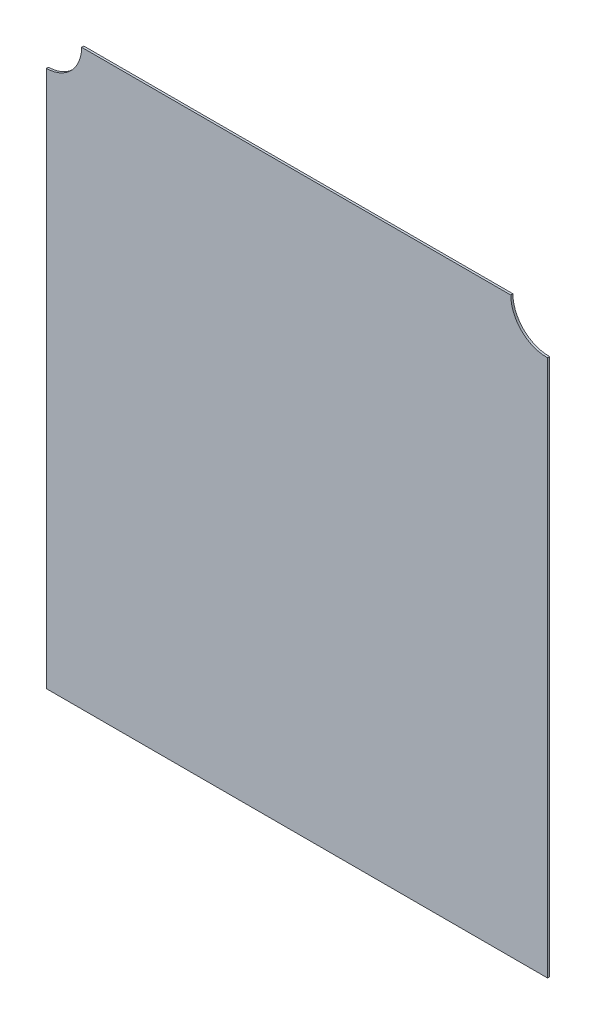
SolidWorks part; units mm, degrees
material "ДСП"
ref_plane "Спереди" through (0, 0, 0) normal (0, 0, 1) x (1, 0, 0)
ref_plane "Сверху" through (0, 0, 0) normal (0, 1, 0) x (1, 0, 0)
ref_plane "Справа" through (0, 0, 0) normal (1, 0, 0) x (0, 0, -1)
sketch "Эскиз1" plane through (0, 0, 0) normal (0, 0, 1) x (1, 0, 0)
  line L1 (0, 0) -> (696, 0)
  line L2 (0, 0) -> (0, 796)
  line L3 (0, 796) -> (696, 796)
  line L4 (696, 0) -> (696, 796)
  dimension "D1" = 796
  dimension "D2" = 696
extrude "Придание толщины" add sketch "Эскиз1" along normal blind 3
sketch "Эскиз3" plane through (0, 0, 3) normal (0, 0, 1) x (1, 0, 0)
  line L0 (0, 796) -> (0, 0) construction
  line L1 (0, 0) -> (696, 0) construction
  circle A0 centre (-1, 796) radius 50
  dimension "D1" = 100
  dimension "D2" = 1
  dimension "D3" = 796
extrude "Отверстие 1" cut sketch "Эскиз3" against normal blind 3
sketch "Эскиз4" plane through (0, 0, 3) normal (0, 0, 1) x (1, 0, 0)
  line L0 (0, 746.01) -> (0, 0) construction
  line L1 (0, 0) -> (696, 0) construction
  circle A0 centre (695, 796) radius 50
  dimension "D3" = 100
  dimension "D1" = 695
  dimension "D2" = 796
extrude "Отверстие 2" cut sketch "Эскиз4" against normal blind 3
sketch "Эскиз5" plane through (0, 0, 3) normal (0, 0, 1) x (1, 0, 0)
  line L0 (0, 746.01) -> (0, 0) construction
  line L1 (0, 0) -> (696, 0) construction
  circle A0 centre (0, 0) radius 4
  dimension "D1" = 8
extrude "Отверстие 3" [suppressed] cut sketch "Эскиз5" against normal blind 16
sketch "Эскиз6" plane through (0, 0, 3) normal (0, 0, 1) x (1, 0, 0)
  line L0 (0, 746.01) -> (0, 0) construction
  line L1 (0, 0) -> (696, 0) construction
  circle A0 centre (0, 0) radius 4
  dimension "D1" = 8
extrude "Отверстие 4" [suppressed] cut sketch "Эскиз6" against normal blind 16
sketch "Эскиз7" plane through (0, 0, 3) normal (0, 0, 1) x (1, 0, 0)
  line L0 (0, 746.01) -> (0, 0) construction
  line L1 (0, 0) -> (696, 0) construction
  circle A0 centre (0, 0) radius 4
  dimension "D1" = 8
extrude "Отверстие 5" [suppressed] cut sketch "Эскиз7" against normal blind 16
sketch "Эскиз8" plane through (0, 0, 3) normal (0, 0, 1) x (1, 0, 0)
  line L0 (0, 746.01) -> (0, 0) construction
  line L1 (0, 0) -> (696, 0) construction
  circle A0 centre (0, 0) radius 4
  dimension "D1" = 8
extrude "Отверстие 6" [suppressed] cut sketch "Эскиз8" against normal blind 16
sketch "Эскиз9" plane through (0, 0, 3) normal (0, 0, 1) x (1, 0, 0)
  line L0 (0, 746.01) -> (0, 0) construction
  line L1 (0, 0) -> (696, 0) construction
  circle A0 centre (0, 0) radius 4
  dimension "D1" = 8
extrude "Отверстие 7" [suppressed] cut sketch "Эскиз9" against normal blind 16
sketch "Эскиз10" plane through (0, 0, 3) normal (0, 0, 1) x (1, 0, 0)
  line L0 (0, 746.01) -> (0, 0) construction
  line L1 (0, 0) -> (696, 0) construction
  circle A0 centre (0, 0) radius 4
  dimension "D1" = 8
extrude "Отверстие 8" [suppressed] cut sketch "Эскиз10" against normal blind 16
sketch "Эскиз27" plane through (0, 0, 3) normal (0, 0, 1) x (1, 0, 0)
  line L2 (0, 746.01) -> (0, 0) construction
  line L3 (0, 0) -> (696, 0) construction
  circle A0 centre (0, 0) radius 4
  dimension "D1" = 8
  dimension "D3" = 0
extrude "Отверстие 9" [suppressed] cut sketch "Эскиз27" against normal blind 10
sketch "Эскиз29" plane through (0, 0, 3) normal (0, 0, 1) x (1, 0, 0)
  line L2 (0, 746.01) -> (0, 0) construction
  line L3 (0, 0) -> (696, 0) construction
  circle A0 centre (0, 0) radius 4
  dimension "D1" = 8
extrude "Отверстие 10" [suppressed] cut sketch "Эскиз29" against normal blind 10
sketch "Эскиз30" plane through (0, 0, 3) normal (0, 0, 1) x (1, 0, 0)
  line L1 (0, 0) -> (696, 0) construction
  line L3 (0, 746.01) -> (0, 0) construction
  circle A0 centre (0, 0) radius 4
  dimension "D1" = 8
extrude "Отверстие 11" [suppressed] cut sketch "Эскиз30" against normal blind 10
sketch "Эскиз31" plane through (0, 0, 3) normal (0, 0, 1) x (1, 0, 0)
  line L2 (0, 0) -> (696, 0) construction
  line L3 (0, 746.01) -> (0, 0) construction
  circle A0 centre (0, 0) radius 4
  dimension "D1" = 8
extrude "Отверстие 12" [suppressed] cut sketch "Эскиз31" against normal blind 10
sketch "Эскиз11" plane through (0, 796, 0) normal (0, 1, 0) x (1, 0, 0)
  line L0 (0, -3) -> (0, 0) construction
  line L1 (645, -3) -> (49, -3) construction
  circle A0 centre (0, -3) radius 2.5
  dimension "D3" = 0
  dimension "D1" = 5
extrude "Отверстие А1" [suppressed] cut sketch "Эскиз11" against normal blind 37
sketch "Эскиз12" plane through (0, 796, 0) normal (0, 1, 0) x (1, 0, 0)
  line L1 (0, -3) -> (0, 0) construction
  line L2 (645, -3) -> (49, -3) construction
  circle A0 centre (0, 5) radius 2.5
  dimension "D1" = 5
  dimension "D3" = 8
extrude "Отверстие А2" [suppressed] cut sketch "Эскиз12" against normal blind 37
sketch "Эскиз13" plane through (0, 796, 0) normal (0, 1, 0) x (1, 0, 0)
  line L1 (0, -3) -> (0, 0) construction
  line L2 (645, -3) -> (49, -3) construction
  circle A0 centre (0, -3) radius 4
  dimension "D1" = 8
  dimension "D3" = 0
extrude "Отверстие А3" [suppressed] cut sketch "Эскиз13" against normal blind 20
sketch "Эскиз14" plane through (0, 796, 0) normal (0, 1, 0) x (1, 0, 0)
  line L0 (0, -3) -> (0, 0) construction
  line L1 (645, -3) -> (49, -3) construction
  circle A0 centre (0, 5) radius 4
  dimension "D1" = 8
  dimension "D3" = 8
extrude "Отверстие А4" [suppressed] cut sketch "Эскиз14" against normal blind 20
sketch "Эскиз15" plane through (696, 0, 0) normal (1, 0, 0) x (0, 0, -1)
  line L0 (-3, 796) -> (0, 796) construction
  line L1 (-3, 0) -> (-3, 746.01) construction
  circle A0 centre (-3, 796) radius 2.5
  dimension "D2" = 0
  dimension "D3" = 0
  dimension "D1" = 5
extrude "Отверстие В1" [suppressed] cut sketch "Эскиз15" against normal blind 37
sketch "Эскиз16" plane through (696, 0, 0) normal (1, 0, 0) x (0, 0, -1)
  line L0 (-3, 796) -> (0, 796) construction
  line L1 (-3, 0) -> (-3, 746.01) construction
  circle A0 centre (-3, 796) radius 2.5
  dimension "D1" = 5
extrude "Отверстие В2" [suppressed] cut sketch "Эскиз16" against normal blind 37
sketch "Эскиз17" plane through (696, 0, 0) normal (1, 0, 0) x (0, 0, -1)
  line L1 (-3, 796) -> (0, 796) construction
  line L2 (-3, 0) -> (-3, 746.01) construction
  circle A0 centre (-3, 796) radius 4
  dimension "D1" = 8
  dimension "D2" = 0
  dimension "D3" = 0
extrude "Отверстие В3" [suppressed] cut sketch "Эскиз17" against normal blind 20
sketch "Эскиз18" plane through (696, 0, 0) normal (1, 0, 0) x (0, 0, -1)
  line L0 (-3, 796) -> (0, 796) construction
  line L1 (-3, 0) -> (-3, 746.01) construction
  circle A0 centre (-3, 796) radius 4
  dimension "D3" = 0
  dimension "D2" = 8
  dimension "D1" = 0
extrude "Отверстие В4" [suppressed] cut sketch "Эскиз18" against normal blind 20
sketch "Эскиз19" plane through (0, 0, 0) normal (0, -1, 0) x (1, 0, 0)
  line L0 (696, 3) -> (696, 0) construction
  line L1 (0, 3) -> (696, 3) construction
  circle A0 centre (696, 3) radius 2.5
  dimension "D2" = 0
  dimension "D3" = 0
  dimension "D1" = 5
extrude "Отверстие С1" [suppressed] cut sketch "Эскиз19" against normal blind 37
sketch "Эскиз20" plane through (0, 0, 0) normal (0, -1, 0) x (1, 0, 0)
  line L0 (696, 3) -> (696, 0) construction
  line L1 (0, 3) -> (696, 3) construction
  circle A0 centre (696, 3) radius 2.5
  dimension "D3" = 0
  dimension "D1" = 0
  dimension "D2" = 5
extrude "Отверстие С2" [suppressed] cut sketch "Эскиз20" against normal blind 37
sketch "Эскиз21" plane through (0, 0, 0) normal (0, -1, 0) x (1, 0, 0)
  line L0 (696, 3) -> (696, 0) construction
  line L1 (0, 3) -> (696, 3) construction
  circle A0 centre (696, 3) radius 4
  dimension "D1" = 8
  dimension "D2" = 0
  dimension "D3" = 0
extrude "Отверстие С3" [suppressed] cut sketch "Эскиз21" against normal blind 20
sketch "Эскиз22" plane through (0, 0, 0) normal (0, -1, 0) x (1, 0, 0)
  line L0 (696, 3) -> (696, 0) construction
  line L1 (0, 3) -> (696, 3) construction
  circle A0 centre (696, 3) radius 4
  dimension "D1" = 8
  dimension "D2" = 0
  dimension "D3" = 0
extrude "Отверстие С4" [suppressed] cut sketch "Эскиз22" against normal blind 20
sketch "Эскиз23" plane through (0, 0, 0) normal (-1, 0, 0) x (0, 0, 1)
  line L0 (3, 0) -> (0, 0) construction
  line L1 (3, 746.01) -> (3, 0) construction
  circle A0 centre (3, 0) radius 2.5
  dimension "D2" = 0
  dimension "D3" = 0
  dimension "D1" = 5
extrude "Отверстие Д1" [suppressed] cut sketch "Эскиз23" against normal blind 37
sketch "Эскиз24" plane through (0, 0, 0) normal (-1, 0, 0) x (0, 0, 1)
  line L0 (3, 0) -> (0, 0) construction
  line L1 (3, 746.01) -> (3, 0) construction
  circle A0 centre (3, 0) radius 2.5
  dimension "D2" = 0
  dimension "D3" = 0
  dimension "D1" = 5
extrude "Отверстие Д2" [suppressed] cut sketch "Эскиз24" against normal blind 37
sketch "Эскиз25" plane through (0, 0, 0) normal (-1, 0, 0) x (0, 0, 1)
  line L0 (3, 0) -> (0, 0) construction
  line L1 (3, 746.01) -> (3, 0) construction
  circle A0 centre (3, 0) radius 4
  dimension "D1" = 8
  dimension "D2" = 0
  dimension "D3" = 0
extrude "Отверстие Д3" [suppressed] cut sketch "Эскиз25" against normal blind 20
sketch "Эскиз26" plane through (0, 0, 0) normal (-1, 0, 0) x (0, 0, 1)
  line L0 (3, 0) -> (0, 0) construction
  line L1 (3, 746.01) -> (3, 0) construction
  circle A0 centre (3, 0) radius 4
  dimension "D1" = 8
  dimension "D2" = 0
  dimension "D3" = 0
extrude "Отверстие Д4" [suppressed] cut sketch "Эскиз26" against normal blind 20
equation "\"D1@Придание толщины\" = \"Thick\""
equation "\"D2@Эскиз1\"=\"Width\""
equation "\"D1@Эскиз1\"=\"Height\""
equation "\"D1\" = 100"
equation "\"X1\" = 1"
equation "\"Y1\" = 796"
equation "\"H1\" = 3"
equation "\"D1@Эскиз3\"=\"D1\""
equation "\"D2@Эскиз3\"=\"X1\""
equation "\"D3@Эскиз3\"=\"Y1\""
equation "\"D1@Отверстие 1\"=\"H1\""
equation "\"D2\" = 100"
equation "\"X2\" = 695"
equation "\"Y2\" = 796"
equation "\"H2\" = 3"
equation "\"D3\" = 0"
equation "\"X3\" = 0"
equation "\"Y3\" = 0"
equation "\"H3\" = 0"
equation "\"D4\" = 0"
equation "\"X4\" = 0"
equation "\"Y4\" = 0"
equation "\"H4\" = 0"
equation "\"D5\" = 0"
equation "\"X5\" = 0"
equation "\"Y5\" = 0"
equation "\"H5\" = 0"
equation "\"D6\" = 0"
equation "\"X6\" = 0"
equation "\"Y6\" = 0"
equation "\"H6\" = 0"
equation "\"D7\" = 0"
equation "\"X7\" = 0"
equation "\"Y7\" = 0"
equation "\"H7\" = 0"
equation "\"D8\" = 0"
equation "\"X8\" = 0"
equation "\"Y8\" = 0"
equation "\"H8\" = 0"
equation "\"D3@Эскиз4\"=\"D2\""
equation "\"D1@Эскиз4\"=\"X2\""
equation "\"D2@Эскиз4\"=\"Y2\""
equation "\"D1@Отверстие 2\"=\"H2\""
equation "\"D2@Эскиз5\"=\"X3\""
equation "\"D1@Эскиз5\"=\"D3\""
equation "\"D3@Эскиз5\"=\"Y3\""
equation "\"D1@Отверстие 3\" = \"H3\""
equation "\"D1@Эскиз6\"=\"D4\""
equation "\"D2@Эскиз6\"=\"X4\""
equation "\"D3@Эскиз6\"=\"Y4\""
equation "\"D1@Отверстие 4\" = \"H4\""
equation "\"D1@Эскиз7\"=\"D5\""
equation "\"D2@Эскиз7\"=\"X5\""
equation "\"D3@Эскиз7\"=\"Y5\""
equation "\"D1@Отверстие 5\" = \"H5\""
equation "\"D1@Эскиз8\"=\"D6\""
equation "\"D2@Эскиз8\"=\"X6\""
equation "\"D3@Эскиз8\"=\"Y6\""
equation "\"D1@Отверстие 6\" = \"H6\""
equation "\"D1@Эскиз9\"=\"D7\""
equation "\"D2@Эскиз9\"=\"X7\""
equation "\"D3@Эскиз9\"=\"Y7\""
equation "\"D1@Отверстие 7\" = \"H7\""
equation "\"D1@Эскиз10\"=\"D8\""
equation "\"D2@Эскиз10\"=\"X8\""
equation "\"D3@Эскиз10\"=\"Y8\""
equation "\"D1@Отверстие 8\" = \"H8\""
equation "\"Отверстие 1\"= IIF ( \"D1\" = 0 , \"suppressed\" , \"unsuppressed\" )"
equation "\"Отверстие 2\"= IIF ( \"D2\" = 0 , \"suppressed\" , \"unsuppressed\" )"
equation "\"Отверстие 3\"= IIF ( \"D3\" = 0 , \"suppressed\" , \"unsuppressed\" )"
equation "\"Отверстие 4\"= IIF ( \"D4\" = 0 , \"suppressed\" , \"unsuppressed\" )"
equation "\"Отверстие 5\"= IIF ( \"D5\" = 0 , \"suppressed\" , \"unsuppressed\" )"
equation "\"Отверстие 6\" = IIF ( \"D6\" = 0 , \"suppressed\" , \"unsuppressed\" )"
equation "\"Отверстие 7\"= IIF ( \"D7\" = 0 , \"suppressed\" , \"unsuppressed\" )"
equation "\"Отверстие 8\"= IIF ( \"D8\" = 0 , \"suppressed\" , \"unsuppressed\" )"
equation "\"DA1\"= 0"
equation "\"XA1\"= 0"
equation "\"YA1\"= 0"
equation "\"HA1\"= 0"
equation "\"DA2\"= 0"
equation "\"XA2\"= 0"
equation "\"YA2\"= 0"
equation "\"HA2\"= 0"
equation "\"DA3\"= 0"
equation "\"XA3\"= 0"
equation "\"YA3\"= 0"
equation "\"DA4\"= 0"
equation "\"XA4\"= 0"
equation "\"YA4\"= 0"
equation "\"HA4\"= 0"
equation "\"D1@Эскиз11\"=\"DA1\""
equation "\"D2@Эскиз11\"=\"XA1\""
equation "\"D3@Эскиз11\"=\"YA1\""
equation "\"D1@Отверстие А1\" = \"HA1\""
equation "\"D1@Эскиз12\"=\"DA2\""
equation "\"D2@Эскиз12\"=\"XA2\""
equation "\"HA3\"= 0"
equation "\"D1@Эскиз13\"=\"DA3\""
equation "\"D2@Эскиз13\"=\"XA3\""
equation "\"D3@Эскиз13\"=\"YA3\""
equation "\"D1@Отверстие А3\" = \"HA3\""
equation "\"D1@Отверстие А2\" = \"HA2\""
equation "\"D1@Эскиз14\"=\"DA4\""
equation "\"D2@Эскиз14\"=\"XA4\""
equation "\"Отверстие А1\"= IIF ( \"DA1\" = 0 , \"suppressed\" , \"unsuppressed\" )"
equation "\"Отверстие А2\"= IIF ( \"DA2\" = 0 , \"suppressed\" , \"unsuppressed\" )"
equation "\"Отверстие А3\"= IIF ( \"DA3\" = 0 , \"suppressed\" , \"unsuppressed\" )"
equation "\"Отверстие А4\"= IIF ( \"DA4\" = 0 , \"suppressed\" , \"unsuppressed\" )"
equation "\"DB1\"= 0"
equation "\"XB1\"= 0"
equation "\"YB1\"= 0"
equation "\"HB1\"= 0"
equation "\"DB2\"= 0"
equation "\"XB2\"= 0"
equation "\"YB2\"= 0"
equation "\"HB2\"= 0"
equation "\"DB3\"= 0"
equation "\"XB3\"= 0"
equation "\"YB3\"= 0"
equation "\"HB3\"= 0"
equation "\"DB4\"= 0"
equation "\"XB4\"= 0"
equation "\"YB4\"= 0"
equation "\"HB4\"= 0"
equation "\"DC1\"= 0"
equation "\"XC1\"= 0"
equation "\"YC1\"= 0"
equation "\"HC1\"= 0"
equation "\"DC2\"= 0"
equation "\"XC2\"= 0"
equation "\"YC2\"= 0"
equation "\"HC2\"= 0"
equation "\"DC3\"= 0"
equation "\"XC3\"= 0"
equation "\"YC3\"= 0"
equation "\"HC3\"= 0"
equation "\"DC4\"= 0"
equation "\"XC4\"= 0"
equation "\"YC4\"= 0"
equation "\"HC4\"= 0"
equation "\"DD1\"= 0"
equation "\"XD1\"= 0"
equation "\"YD1\"= 0"
equation "\"HD1\"= 0"
equation "\"DD2\"= 0"
equation "\"XD2\"= 0"
equation "\"YD2\"= 0"
equation "\"HD2\"= 0"
equation "\"DD3\"= 0"
equation "\"XD3\"= 0"
equation "\"YD3\"= 0"
equation "\"HD3\"= 0"
equation "\"DD4\"= 0"
equation "\"XD4\"= 0"
equation "\"YD4\"= 0"
equation "\"HD4\"= 0"
equation "\"D1@Эскиз15\"=\"DB1\""
equation "\"D2@Эскиз15\"=\"XB1\""
equation "\"D3@Эскиз15\"=\"YB1\""
equation "\"D1@Отверстие В1\" = \"HB1\""
equation "\"D1@Эскиз16\"=\"DB2\""
equation "\"D2@Эскиз16\"=\"XB2\""
equation "\"D3@Эскиз16\"=\"YB2\""
equation "\"D1@Отверстие В2\" = \"HB2\""
equation "\"D1@Эскиз17\"=\"DB3\""
equation "\"D2@Эскиз17\"=\"XB3\""
equation "\"D3@Эскиз17\"=\"YB3\""
equation "\"D1@Отверстие В3\" = \"HB3\""
equation "\"D1@Эскиз18\"=\"XB4\""
equation "\"D2@Эскиз18\"=\"DB4\""
equation "\"D3@Эскиз18\"=\"YB4\""
equation "\"D1@Отверстие В4\" = \"HB4\""
equation "\"D1@Эскиз19\"=\"DC1\""
equation "\"D2@Эскиз19\"=\"XC1\""
equation "\"D3@Эскиз19\"=\"YC1\""
equation "\"D1@Отверстие С1\" = \"HC1\""
equation "\"D1@Эскиз20\"=\"XC2\""
equation "\"D2@Эскиз20\"=\"DC2\""
equation "\"D3@Эскиз20\"=\"YC2\""
equation "\"D1@Отверстие С2\" = \"HC2\""
equation "\"D1@Эскиз21\"=\"DC3\""
equation "\"D2@Эскиз21\"=\"XC3\""
equation "\"D3@Эскиз21\"=\"YC3\""
equation "\"D1@Отверстие С3\" = \"HC3\""
equation "\"D1@Эскиз22\"=\"DC4\""
equation "\"D2@Эскиз22\"=\"XC4\""
equation "\"D3@Эскиз22\"=\"YC4\""
equation "\"D1@Отверстие С4\" = \"HC4\""
equation "\"D1@Эскиз23\"=\"DD1\""
equation "\"D2@Эскиз23\"=\"XD1\""
equation "\"D3@Эскиз23\"=\"YD1\""
equation "\"D1@Отверстие Д1\" = \"HD1\""
equation "\"D1@Эскиз24\"=\"DD2\""
equation "\"D2@Эскиз24\"=\"XD2\""
equation "\"D3@Эскиз24\"=\"YD2\""
equation "\"D1@Отверстие Д2\" = \"HD2\""
equation "\"D1@Эскиз25\"=\"DD3\""
equation "\"D2@Эскиз25\"=\"XD3\""
equation "\"D3@Эскиз25\"=\"YD3\""
equation "\"D1@Отверстие Д3\" = \"HD3\""
equation "\"D1@Эскиз26\"=\"DD4\""
equation "\"D2@Эскиз26\"=\"XD4\""
equation "\"D3@Эскиз26\"=\"YD4\""
equation "\"D1@Отверстие Д4\" = \"HD4\""
equation "\"Отверстие В1\"= IIF ( \"DB1\" = 0 , \"suppressed\" , \"unsuppressed\" )"
equation "\"Отверстие В2\"= IIF ( \"DB2\" = 0 , \"suppressed\" , \"unsuppressed\" )"
equation "\"Отверстие В3\"= IIF ( \"DB3\" = 0 , \"suppressed\" , \"unsuppressed\" )"
equation "\"Отверстие В4\"= IIF ( \"DB4\" = 0 , \"suppressed\" , \"unsuppressed\" )"
equation "\"Отверстие С1\"= IIF ( \"DC1\" = 0 , \"suppressed\" , \"unsuppressed\" )"
equation "\"Отверстие С2\"= IIF ( \"DC2\" = 0 , \"suppressed\" , \"unsuppressed\" )"
equation "\"Отверстие С3\"= IIF ( \"DC3\" = 0 , \"suppressed\" , \"unsuppressed\" )"
equation "\"Отверстие С4\"= IIF ( \"DC4\" = 0 , \"suppressed\" , \"unsuppressed\" )"
equation "\"Отверстие Д1\"= IIF ( \"DD1\" = 0 , \"suppressed\" , \"unsuppressed\" )"
equation "\"Отверстие Д2\"= IIF ( \"DD2\" = 0 , \"suppressed\" , \"unsuppressed\" )"
equation "\"Отверстие Д3\"= IIF ( \"DD3\" = 0 , \"suppressed\" , \"unsuppressed\" )"
equation "\"Отверстие Д4\"= IIF ( \"DD4\" = 0 , \"suppressed\" , \"unsuppressed\" )"
equation "\"D9\" = 0"
equation "\"X9\" = 0"
equation "\"Y9\" = 0"
equation "\"H9\" = 0"
equation "\"D10\" = 0"
equation "\"X10\" = 0"
equation "\"Y10\" = 0"
equation "\"H10\" = 0"
equation "\"D11\" = 0"
equation "\"X11\" = 0"
equation "\"Y11\" = 0"
equation "\"H11\" = 0"
equation "\"D12\" = 0"
equation "\"X12\" = 0"
equation "\"Y12\" = 0"
equation "\"H12\" = 0"
equation "\"D1@Эскиз27\"=\"D9\""
equation "\"D2@Эскиз27\"=\"X9\""
equation "\"D3@Эскиз27\"=\"Y9\""
equation "\"D1@Отверстие 9\" = \"H9\""
equation "\"D1@Эскиз29\"=\"D10\""
equation "\"D2@Эскиз29\"=\"X10\""
equation "\"D3@Эскиз29\"=\"Y10\""
equation "\"D1@Отверстие 10\" = \"H10\""
equation "\"D1@Эскиз30\"=\"D11\""
equation "\"D2@Эскиз30\"=\"X11\""
equation "\"D3@Эскиз30\"=\"Y11\""
equation "\"D1@Отверстие 11\" = \"H11\""
equation "\"D1@Эскиз31\"=\"D12\""
equation "\"D2@Эскиз31\"=\"X12\""
equation "\"D3@Эскиз31\"=\"Y12\""
equation "\"D1@Отверстие 12\" = \"H12\""
equation "\"Отверстие 9\"= IIF ( \"D9\" = 0 , \"suppressed\" , \"unsuppressed\" )"
equation "\"Отверстие 10\"= IIF ( \"D10\" = 0 , \"suppressed\" , \"unsuppressed\" )"
equation "\"Отверстие 11\"= IIF ( \"D11\" = 0 , \"suppressed\" , \"unsuppressed\" )"
equation "\"Отверстие 12\"= IIF ( \"D12\" = 0 , \"suppressed\" , \"unsuppressed\" )"
equation "\"Height\" = 796"
equation "\"Width\" = 696"
equation "\"Thick\" = 3"
